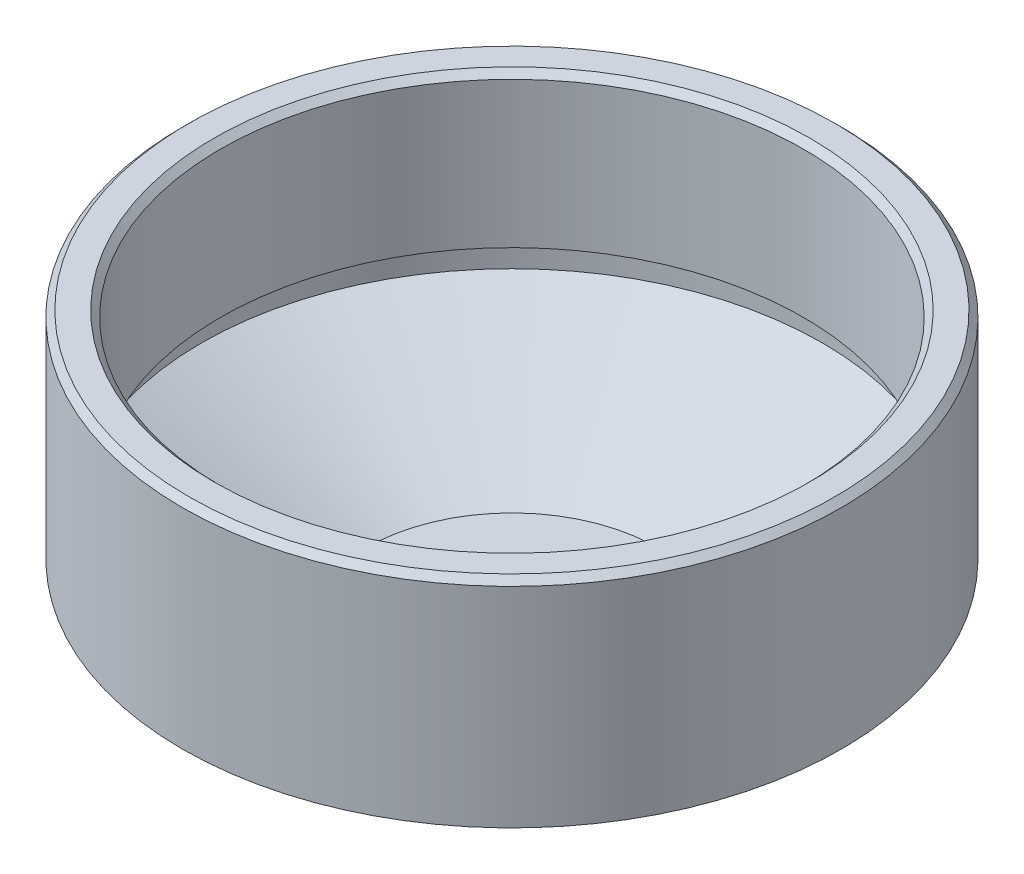
SolidWorks part; units mm, degrees
material "AISI 304"
ref_plane "Спереди" through (0, 0, 0) normal (0, 0, 1) x (1, 0, 0)
ref_plane "Сверху" through (0, 0, 0) normal (0, 1, 0) x (1, 0, 0)
ref_plane "Справа" through (0, 0, 0) normal (1, 0, 0) x (0, 0, -1)
ref_axis "ОсьX" through (-88.99, 0, 0) along (1, 0, 0)
ref_axis "ОсьZ" through (0, 55, 0) along (0, -1, 0)
ref_axis "ОсьY" through (0, 0, -88.99) along (0, 0, 1)
sketch "Эскиз1" plane through (0, 0, 0) normal (0, 0, 1) x (1, 0, 0)
  line L0 (-26, 28) -> (-26, 11)
  line L1 (0, 26.169) -> (0, -22.1581) construction
  line L2 (-6.9474, 0) -> (-3, 0)
  line L3 (-3, 0) -> (-3, 6)
  line L4 (-3, 6) -> (-11.5096, 6)
  line L5 (-24.5, 13.5) -> (-24.5, 16)
  line L6 (-24.5, 16) -> (-23, 16)
  line L7 (-23, 16) -> (-23, 28)
  line L8 (-23, 28) -> (-26, 28)
  line L11 (-26, 11) -> (-6.9474, 0)
  line L12 (-24.5, 13.5) -> (-11.5096, 6)
  dimension "D1" = 52
  dimension "D2" = 60
  dimension "D3" = 46
  dimension "D4" = 6
  dimension "D5" = 6
  dimension "D6" = 17
  dimension "D7" = 1.5
  dimension "D8" = 2.5
  dimension "D9" = 12
  dimension "D10" = 28
revolve "Повернуть1" add sketch "Эскиз1" angle 360 mid plane about L1
cosmetic thread "Условное изображение резьбы1" parameters "D2"=48
cosmetic thread "Условное изображение резьбы2" parameters "D2"=8
chamfer "Фаска1" distance 0.5 angle 45 3 edges at (0, 0, 3) (0, 28, 26) (0, 28, 23)
